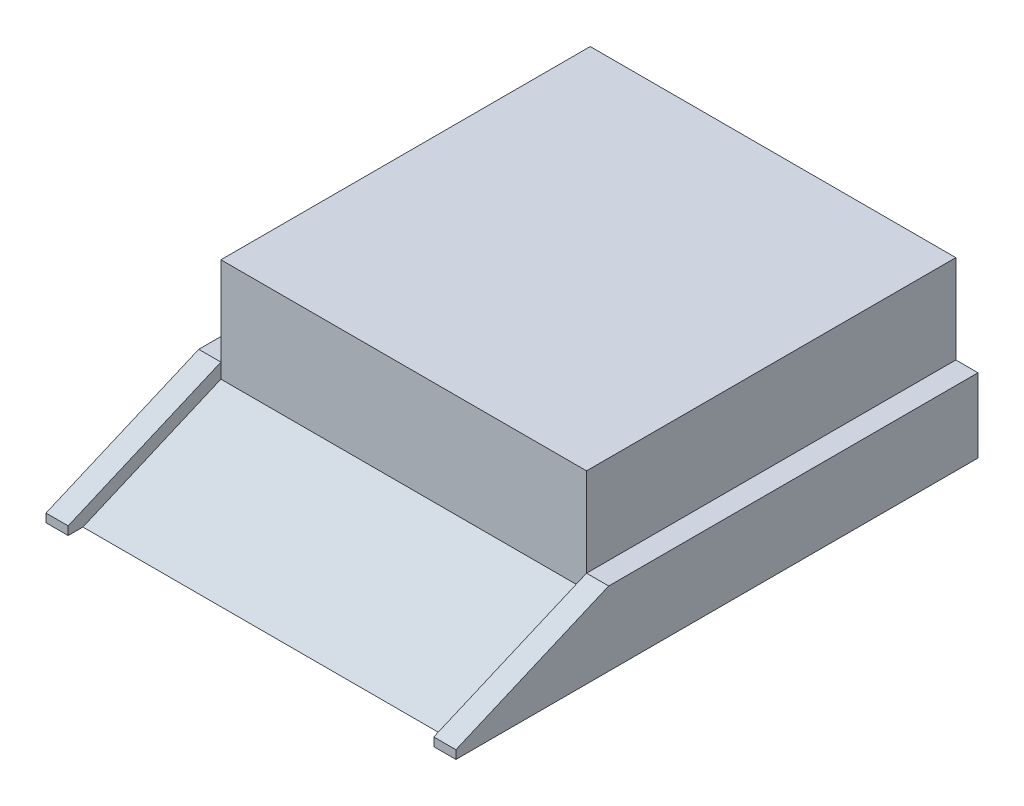
SolidWorks part; units mm, degrees
note: The reader was unsure of these and kept them because the rebuilt part matched: shared geometry of "草图2<3>".
ref_plane "前视基准面" through (0, 0, 0) normal (0, 0, 1) x (1, 0, 0)
ref_plane "上视基准面" through (0, 0, 0) normal (0, 1, 0) x (1, 0, 0)
ref_plane "右视基准面" through (0, 0, 0) normal (1, 0, 0) x (0, 0, -1)
sketch "草图1" plane through (0, 0, 0) normal (0, 1, 0) x (1, 0, 0)
  line L1 (-1387.5, 1767) -> (1387.5, 1767)
  line L2 (-1387.5, 1767) -> (-1387.5, -1767)
  line L3 (-1387.5, -1767) -> (1387.5, -1767)
  line L4 (1387.5, 1767) -> (1387.5, -1767)
  line L5 (0, -1767) -> (0, 1767) construction
  line L6 (-1387.5, 0) -> (1387.5, 0) construction
  point P0 (0, 0)
  dimension "D1" = 2775
  dimension "D2" = 3534
extrude "凸台-拉伸1" add sketch "草图1" along normal blind 500
sketch "草图2" plane through (1387.5, 0, 0) normal (1, 0, 0) x (0, 0, -1)
  line L0 (1767, 400) -> (-733, 400)
  line L1 (1767, 500) -> (1767, 0) construction
  line L2 (-733, 400) -> (-1667, 0)
  line L3 (-1767, 500) -> (-1767, 0) construction
  line L5 (-1767, 0) -> (1767, 0) construction
  line L6 (-1667, 0) -> (-733, 0)
  line L8 (1767, 400) -> (1767, 0)
  line L9 (1767, 0) -> (-733, 0)
  line L10 (-1667, 0) -> (-1767, 0)
  line L11 (-1767, 0) -> (-1767, 57.1734)
  line L12 (-733, 400) -> (-733, 500)
  line L13 (-1767, 500) -> (1767, 500) construction
  line L14 (-733, 0) -> (-733, 400)
  line L15 (1767, 400) -> (1767, 500)
  line L16 (1767, 500) -> (-1767, 500)
  line L17 (-1767, 500) -> (-1767, 57.1734)
  line L18 (-733, 500) -> (-1767, 57.1734)
  line M1 (-1767, 0) -> (1767, 0)
  line M2 (1767, 0) -> (1767, 500)
  line M3 (1767, 500) -> (-1767, 500)
  line M4 (-1767, 500) -> (-1767, 0)
  dimension "D1" = 2500
  dimension "D2" = 100
  dimension "D4" = 100
extrude "切除-拉伸1" cut sketch "草图2" against normal through all contours L18 M3 M4
extrude "切除-拉伸2" cut sketch "草图2<3>" against normal blind 2475 from offset 150 contours L12 L18 L2 M4 M1 | L12 L0 M2 M3 offset against normal yes
sketch "草图2<3>" plane through (1387.5, 0, 0) normal (1, 0, 0) x (0, 0, -1) same geometry as "草图2"
sketch "草图3" plane through (0, 400, 0) normal (0, 1, 0) x (1, 0, 0)
  line L0 (1237.5, 1767) -> (-1237.5, -733) construction
  line L1 (1237.5, 1767) -> (1237.5, -733) construction
  line L2 (1237.5, 1767) -> (1237.5, -733) construction
  line L4 (-1150, 1667) -> (1150, 1667)
  line L5 (-1150, 1667) -> (-1150, -633)
  line L6 (-1150, -633) -> (1150, -633)
  line L7 (1150, 1667) -> (1150, -633)
  line L8 (0, -633) -> (0, 1667) construction
  line L9 (-1150, 517) -> (1150, 517) construction
  point P11 (0, 517)
  line M3 (1237.5, 1767) -> (-1237.5, 1767)
  line M5 (-1237.5, -733) -> (1237.5, -733)
  dimension "D1" = 2300
  dimension "D2" = 2300
extrude "凸台-拉伸2" add sketch "草图3" along normal blind 1100 from surface at -400 contours L7 L5 M3 M5 | L7 L5 L6 M5 | L7 L4 L5 M3
